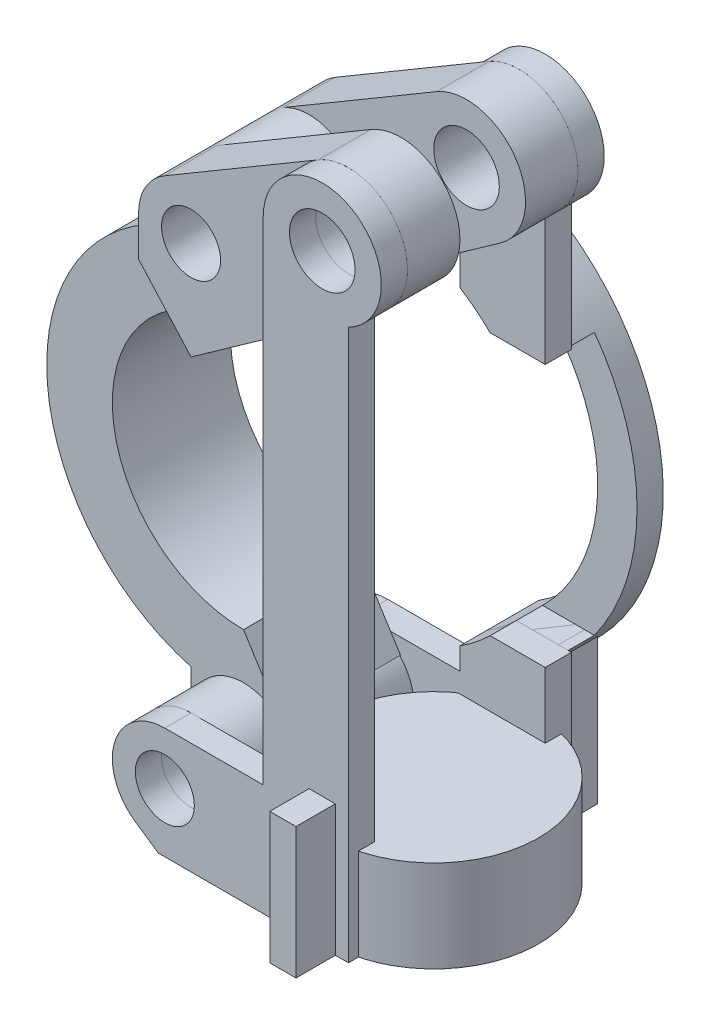
SolidWorks part; units mm, degrees
ref_plane "Front" through (0, 0, 0) normal (0, 0, 1) x (1, 0, 0)
ref_plane "Top" through (0, 0, 0) normal (0, 1, 0) x (1, 0, 0)
ref_plane "Right" through (0, 0, 0) normal (1, 0, 0) x (0, 0, -1)
sketch "Эскиз1" plane through (0, 0, 0) normal (0, 0, 1) x (1, 0, 0)
  line L2 (-12, -6.5) -> (-12, -41.5) construction
  line L3 (-8.6164, -8.6333) -> (-12, -14)
  line L4 (-12, -34) -> (-8.6164, -39.3667)
  line L5 (-16, -6.5) -> (-16, -9.5432)
  line L6 (-16, -41.5) -> (-16, -38.4568)
  line L7 (-14.0327, -3.055) -> (-2.2868, 3.8756)
  line L8 (2.5986, -3.6738) -> (-12, -14)
  circle A0 centre (0, 0) radius 2.5
  circle A1 centre (0, 0) radius 4.5
  circle A2 centre (-12, -6.5) radius 2.25
  circle A3 centre (-12, -41.5) radius 2.25
  arc A4 (-8.6164, -8.6333) -> (-16, -6.5) centre (-12, -6.5) ccw
  arc A5 (-16, -41.5) -> (-9.1226, -38.7214) centre (-12, -41.5) ccw
  arc A6 (-12, -14) -> (-12, -34) centre (-12, -24) ccw
  arc A8 (-16, -9.5432) -> (-16, -38.4568) centre (-12, -24) ccw
  arc A9 (-9.1226, -38.7214) -> (-9.0343, -38.7039) centre (-12, -24) ccw
  dimension "D1" = 5
  dimension "D2" = 9
  dimension "D3" = 4.5
  dimension "D7" = 8
  dimension "D8" = 20
  dimension "D4" = 35
  dimension "D5" = 12
  dimension "D6" = 6.5
extrude "Бобышка-Вытянуть1" add sketch "Эскиз1" along normal blind 4 contours A1 A0 | A4 L3 L8 A1 L7 | A2 L3 A4 L5 A8 L6 A5 A9 L4 A3 A6 region at (-6.201, -4.6653, 0) region at (-10.7059, -11.0659, 0) region at (-3.6711, -2.3757, 0)
sketch "Эскиз2" plane through (0, 0, 4) normal (0, 0, 1) x (1, 0, 0)
  line L0 (-8.0888, -5.6617) -> (-7.0519, -10.5)
  line L1 (2.5986, -3.6738) -> (-12, -14) construction
  circle A0 centre (-12, -6.5) radius 4
  point P7 (-12, -10.5)
  arc M3 (-14.0327, -3.055) -> (-16, -6.5) centre (-12, -6.5) ccw
  line M4 (-16, -6.5) -> (-16, -9.5432)
  arc M5 (-16, -9.5432) -> (-16, -38.4568) centre (-12, -24) ccw
  line M6 (-16, -38.4568) -> (-16, -41.5)
  arc M7 (-16, -41.5) -> (-9.1226, -38.7214) centre (-12, -41.5) ccw
  arc M8 (-9.1226, -38.7214) -> (-9.0343, -38.7039) centre (-12, -24) ccw
  line M9 (-9.0343, -38.7039) -> (-12, -34)
  arc M10 (-12, -34) -> (-12, -14) centre (-12, -24) cw
  line M11 (-12, -14) -> (2.5986, -3.6738)
  circle M14 centre (-12, -41.5) radius 2.25
  circle M15 centre (-12, -6.5) radius 2.25
  dimension "D1" = 8
extrude "Бобышка-Вытянуть2" add sketch "Эскиз2" along normal blind 5 contours A0 L0 M4 M5 M6 M7 M8 M9 M10 M11 M14 | A0 M3 M15 region at (-8.006, -8.1742, 4) region at (-8.1348, -6.0904, 4)
sketch "Эскиз5" plane through (0, 0, 9) normal (0, 0, 1) x (1, 0, 0)
  line L0 (-14.0327, -3.055) -> (-2.2868, 3.8756)
  line L1 (-12, -14) -> (-16, -9.5432)
  line L2 (-16, -9.5432) -> (-16, -6.5)
  line L3 (-12, -14) -> (2.5986, -3.6738)
  circle A0 centre (-12, -6.5) radius 2.25
  circle A1 centre (0, 0) radius 2.5
  circle A3 centre (-12, -6.5) radius 4
  circle A4 centre (0, 0) radius 4.5
  point P10 (-12, -14)
  line M4 (-7.0519, -10.5) -> (-8.0888, -5.6617)
  arc M5 (-8.0888, -5.6617) -> (-16, -6.5) centre (-12, -6.5) ccw
  line M6 (-16, -6.5) -> (-16, -9.5432)
  line M13 (-12, -14) -> (-7.0519, -10.5)
  circle M15 centre (-12, -6.5) radius 2.25
  dimension "D1" = 5
  dimension "D2" = 4.5
  dimension "D3" = 8
  dimension "D4" = 9
extrude "Бобышка-Вытянуть3" add sketch "Эскиз5" along normal blind 4 contours A4 L0 L3 M5 M4 | A3 M5 M15 | A3 L1 M6 M13 M4 | A4 A1 region at (-5.8149, -3.8355, 9) region at (-10.4389, -2.9404, 9) region at (2.1684, 3.7972, 9) region at (-11.1579, -10.8253, 9)
sketch "Эскиз6" plane through (0, 0, 13) normal (0, 0, 1) x (1, 0, 0)
  line L0 (0, 0) -> (0, -47.8505) construction
  line L1 (2, -4.0311) -> (2, -46)
  line L2 (2, -46) -> (-4.5, -46)
  line L3 (-4.5, -46) -> (-4.5, 0)
  line L4 (-4.5, -46) -> (-12.5, -46)
  line L5 (-12.5, -46) -> (-14.2529, -44.8052)
  line L6 (-12, -37.5) -> (-4.5, -37.5)
  line L7 (2, -4.0973) -> (2.5986, -3.6738)
  line L8 (-12, -14) -> (2.5986, -3.6738) construction
  circle A0 centre (0, 0) radius 2.5
  circle A1 centre (0, 0) radius 4.5
  circle A2 centre (-12, -41.5) radius 2.25
  circle A3 centre (-12, -41.5) radius 4
  line M5 (-12, -14) -> (2.5986, -3.6738)
  arc M6 (2.5986, -3.6738) -> (-2.2868, 3.8756) centre (0, 0) ccw
  circle M12 centre (0, 0) radius 2.5
  dimension "D1" = 9
  dimension "D2" = 5
  dimension "D5" = 4.5
  dimension "D6" = 8
  dimension "D3" = 2
  dimension "D4" = 46
  dimension "D7" = 8
extrude "Бобышка-Вытянуть6" add sketch "Эскиз6" along normal blind 2 separate body contours L0 L3 L2 M5 | L0 L2 L1 M5 | L0 A1 L3 M5 | A1 M12 M6 | A3 L5 L4 L3 L6 | A3 A2 | A1 L0 L1 M5 region at (-3.092, -3.092, 13) region at (0.6535, -4.7371, 13) region at (-2.9212, -5.2958, 13) region at (1.0057, -25.4003, 13) region at (-2.2193, -26.5409, 13) region at (-6.9993, -41.9678, 13) region at (-9.2516, -38.7516, 13)
extrude "Бобышка-Вытянуть8" add sketch "Эскиз6<3>" against normal up to surface (4 mm away) separate body contours A3 A2 region at (-9.2516, -38.7516, 13) up to face at (-9.75, -41.5, 9)
sketch "Эскиз6<3>" plane through (0, 0, 13) normal (0, 0, 1) x (1, 0, 0) same geometry as "Эскиз6"
sketch "Эскиз7" plane through (0, 0, 0) normal (0, 0, -1) x (-1, 0, 0)
  line L0 (0, 0) -> (0, -48.7272) construction
  line L1 (-2, -46) -> (-2, -4.0311)
  line L2 (-2, -46) -> (12.5, -46)
  line L3 (12.5, -46) -> (14.2529, -44.8052)
  line L4 (12, -37.5) -> (4.5, -37.5)
  line L5 (4.5, -37.5) -> (4.5, 0)
  circle A0 centre (0, 0) radius 2.5
  circle A1 centre (0, 0) radius 4.5
  circle A2 centre (12, -41.5) radius 2.25
  circle A3 centre (12, -41.5) radius 4
  arc M5 (2.2868, 3.8756) -> (-2.5986, -3.6738) centre (0, 0) ccw
  line M6 (-2.5986, -3.6738) -> (12, -14)
  line M8 (12, -34) -> (9.0343, -38.7039)
  arc M9 (9.0343, -38.7039) -> (9.1226, -38.7214) centre (12, -24) ccw
  arc M10 (9.1226, -38.7214) -> (16, -41.5) centre (12, -41.5) ccw
  circle M15 centre (0, 0) radius 2.5
  circle M16 centre (12, -41.5) radius 2.25
  dimension "D1" = 9
  dimension "D2" = 5
  dimension "D3" = 4.5
  dimension "D4" = 8
  dimension "D5" = 14.5
extrude "Бобышка-Вытянуть9" add sketch "Эскиз7" along normal blind 2 separate body contours L0 L2 L3 L4 L5 M6 M10 M9 M8 | L0 L1 L2 M6 | A1 L0 L5 M6 | A1 M15 M5 | L0 A1 L1 M6 | A3 M10 M16 | A3 L4 M8 M9 region at (0.9981, -4.2573, 0) region at (-2.9212, -5.2958, 0) region at (0.6535, -4.7371, 0) region at (-3.0699, -29.3341, 0) region at (1.0057, -25.4003, 0) region at (-9.0286, -44.0057, 0) region at (-10.039, -37.8618, 0)
sketch "Эскиз9" plane through (0, 0, -2) normal (0, 0, -1) x (-1, 0, 0)
  line L0 (12, -6.5) -> (12, -41.5) construction
  line L1 (-2, -14) -> (2.202, -14)
  line L2 (-2, -46) -> (-2, -4.0311) construction
  line L3 (-2, -34) -> (2.202, -34)
  circle A0 centre (12, -24) radius 14
  line M4 (4.5, -37.5) -> (4.5, 0)
  line M6 (-2, -4.0311) -> (-2, -46)
  dimension "D1" = 28
  dimension "D2" = 20
extrude "Вырез-Вытянуть1" cut sketch "Эскиз9" against normal up to surface (2 mm away) contours A0 M4 | A0 L1 M6 | A0 L3 M6 region at (0.7801, -16.4187, -2) region at (-1.8401, -24, -2) region at (0.7801, -31.5813, -2) up to face at (-6.1182, -29.8807, 0)
sketch "Эскиз10" plane through (0, 0, -2) normal (0, 0, -1) x (-1, 0, 0)
  line L0 (12, -6.5) -> (12, -41.5) construction
  line L1 (4.5, -37.5) -> (1.668, -37.5)
  line L2 (-1.7477, -34) -> (2.202, -34)
  line L3 (4.5, -37.5) -> (4.5, -35.8216)
  circle A0 centre (12, -24) radius 14
  circle A1 centre (12, -24) radius 17
  line M3 (-2, -14) -> (2.202, -14)
  arc M4 (2.202, -14) -> (4.5, -12.1784) centre (12, -24) cw
  line M5 (4.5, -12.1784) -> (4.5, 0)
  dimension "D1" = 28
  dimension "D2" = 34
extrude "Бобышка-Вытянуть10" add sketch "Эскиз10" along normal blind 2 separate body contours L2 A1 L1 L3 A0 | A1 M5 M3 M4 region at (-1.7833, -35.6836, -2) region at (-2.0581, -11.9335, -2)
sketch "Эскиз11" plane through (0, 0, -4) normal (0, 0, -1) x (-1, 0, 0)
  line L0 (12, -6.5) -> (12, -41.5) construction
  line L1 (4.5, -8.7439) -> (4.5, -39.2561)
  line L2 (1.668, -37.5) -> (4.5, -37.5)
  circle A0 centre (12, -24) radius 14
  circle A1 centre (12, -24) radius 17
  line M1 (4.5, -12.1784) -> (4.5, -8.7439)
  arc M2 (4.5, -8.7439) -> (-1.7477, -14) centre (12, -24) ccw
  line M3 (-1.7477, -14) -> (2.202, -14)
  arc M4 (2.202, -14) -> (4.5, -12.1784) centre (12, -24) cw
  dimension "D1" = 28
  dimension "D2" = 34
extrude "Бобышка-Вытянуть11" add sketch "Эскиз11" along normal blind 2 contours M4 M1 M2 M3 | A1 L2 L1 A0 M3 region at (-2.0581, -11.9335, -4) region at (-0.2272, -14.2535, -4)
sketch "Эскиз12" plane through (0, -46, 0) normal (0, -1, 0) x (1, 0, 0)
  line L0 (0, 15) -> (0, -2) construction
  line L1 (2, 15) -> (-12.5, 15) construction
  line L2 (-4.5, -2) -> (-1.668, -2) construction
  line L3 (2, 15) -> (2, 13) construction
  circle A0 centre (0, 6.5) radius 8
  dimension "D2" = 16
  dimension "D1" = 2
extrude "Бобышка-Вытянуть12" add sketch "Эскиз12" against normal blind 7 separate body
sketch "Эскиз13" plane through (0, -46, 0) normal (0, -1, 0) x (1, 0, 0)
  circle A0 centre (0, 6.5) radius 5.5
  point P0 (0, 6.5)
  dimension "D1" = 11
extrude "Вырез-Вытянуть2" cut sketch "Эскиз13" against normal blind 5.1
sketch "Эскиз14" plane through (0, 0, 15) normal (0, 0, 1) x (1, 0, 0)
  line L0 (0, 0) -> (0, -46) construction
  line L1 (2, -46) -> (-12.5, -46) construction
  line L3 (-1, -46) -> (1, -46)
  line L4 (-1, -46) -> (-1, -36)
  line L5 (-1, -36) -> (1, -36)
  line L6 (1, -46) -> (1, -36)
  dimension "D1" = 10
  dimension "D2" = 2
extrude "Бобышка-Вытянуть13" add sketch "Эскиз14" along normal blind 3
sketch "Эскиз15" plane through (0, 0, -2) normal (0, 0, -1) x (-1, 0, 0)
  line L0 (0, 0) -> (0, -46) construction
  line L1 (-2, -46) -> (12.5, -46) construction
  line L3 (-1, -46) -> (1, -46)
  line L4 (-1, -46) -> (-1, -34)
  line L5 (-1, -34) -> (1, -34)
  line L6 (1, -46) -> (1, -34)
  dimension "D1" = 12
  dimension "D2" = 2
extrude "Бобышка-Вытянуть14" add sketch "Эскиз15" along normal blind 3
